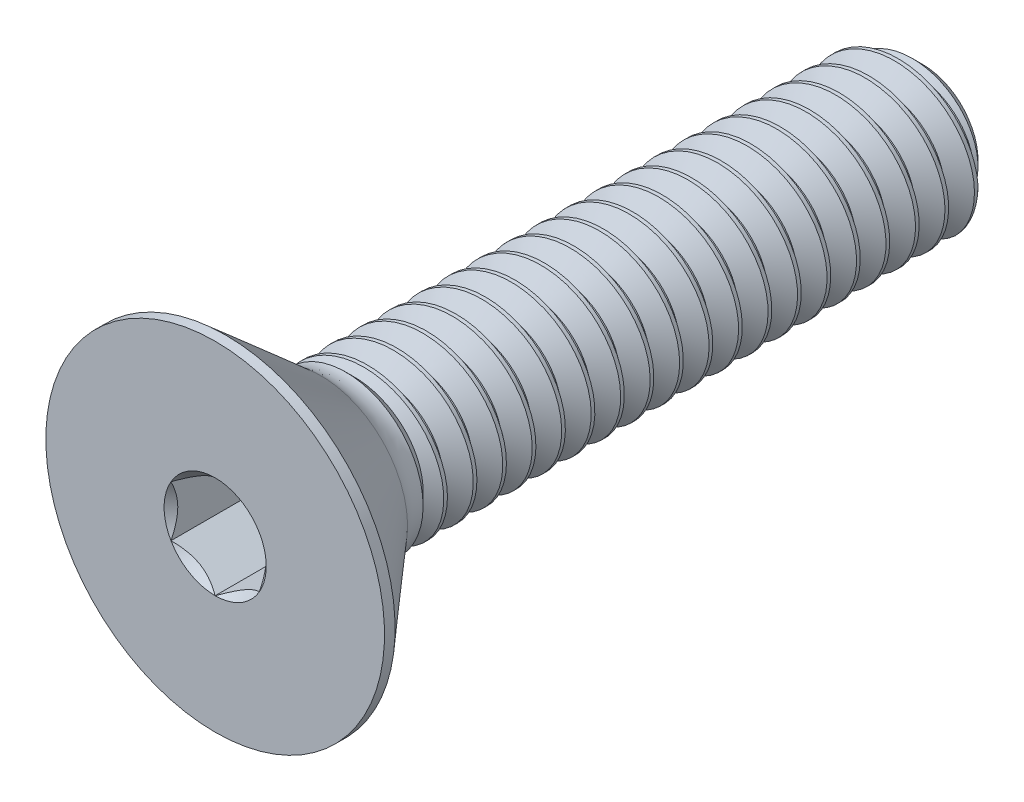
SolidWorks part; units mm, degrees
ref_plane "Front" through (0, 0, 0) normal (0, 0, 1) x (1, 0, 0)
ref_plane "Top" through (0, 0, 0) normal (0, 1, 0) x (1, 0, 0)
ref_plane "Right" through (0, 0, 0) normal (1, 0, 0) x (0, 0, -1)
sketch "Sketch1" plane through (0, 0, 0) normal (1, 0, 0) x (0, 0, -1)
  line L0 (0, 4.5593) -> (0.2845, 4.5593) construction
  line L1 (0.2845, 4.5593) -> (2.8448, 2.3336) construction
  line L2 (0, 2.0828) -> (19.05, 2.0828)
  line L3 (19.05, 2.0828) -> (19.05, 0)
  line L4 (19.05, 0) -> (0, 0)
  line L5 (0, 0) -> (0, 4.5593) construction
  line L6 (0, 4.5593) -> (0, -4.5593) construction
  line L7 (19.05, 2.0828) -> (19.05, -2.0828) construction
  line L8 (0, -4.5593) -> (0.2845, -4.5593) construction
  line L9 (0.2845, -4.5593) -> (2.8448, -2.3336) construction
  line L11 (0, 2.0828) -> (0, 0)
  line L12 (3.5157, 2.0828) -> (3.5157, 0) construction
  arc A1 (2.8448, 2.3336) -> (3.5157, 2.0828) centre (3.5157, 3.1055) ccw construction
  dimension "D1" = 0.2845
  dimension "Head Ht" = 2.8448
  dimension "Head Dia" = 9.1186
  dimension "Dia" = 4.1656
  dimension "Lg" = 19.05
  dimension "Head Angle" = 82
revolve "Revolve1" add sketch "Sketch1" angle 360 mid plane about L4
sketch "Sketch3" plane through (0, 0, -19.05) normal (0, 0, -1) x (-1, 0, 0)
  circle A0 centre (0, 0) radius 2.0828
curve "Helix/Spiral1" pitch 0.7937 height 19.05 radius 2.0828 centre (0, 0, -19.05) axis (0, 0, 1) start towards (0, 1, 0)
sketch "Sketch2" plane through (0, 0, 0) normal (1, 0, 0) x (0, 0, -1)
  line L0 (19.05, 2.0828) -> (19.7445, 2.0828)
  line L1 (19.7445, 2.0828) -> (19.4469, 1.5672)
  line L2 (19.4469, 1.5672) -> (19.3477, 1.5672)
  line L3 (19.3477, 1.5672) -> (19.05, 2.0828)
  line L4 (19.1988, 1.825) -> (19.5957, 1.825) construction
  dimension "D1" = 60
  dimension "D2" = 0.0992
  dimension "D3" = 0.3969
chamfer "Chamfer1" distance 0.5953 angle 45 1 edges at (0, 2.0828, -19.05)
sweep "Cut-Sweep1" cut profiles "Sketch2" path "Helix/Spiral1"
sketch "Sketch7" plane through (0, 0, 0) normal (1, 0, 0) x (0, 0, -1)
  line L0 (0, 4.5593) -> (0.2845, 4.5593) construction
  line L1 (0.2845, 4.5593) -> (2.8448, 2.3336) construction
  line L2 (0, 4.5593) -> (0.2845, 4.5593)
  line L3 (0.2845, 4.5593) -> (2.8448, 2.3336)
  line L4 (3.5157, 2.0828) -> (3.5157, 0) construction
  line L5 (3.5157, 2.0828) -> (3.5157, 0)
  line L7 (0, 0) -> (0, 4.5593) construction
  line L8 (0, 0) -> (0, 4.5593)
  line L9 (0, 0) -> (3.5157, 0)
  line L10 (5.0152, 0) -> (-5.0152, 0) construction
  arc A0 (2.8448, 2.3336) -> (3.5157, 2.0828) centre (3.5157, 3.1055) ccw construction
  arc A1 (2.8448, 2.3336) -> (3.5157, 2.0828) centre (3.5157, 3.1055) ccw
revolve "Revolve2" add sketch "Sketch7" angle 360 mid plane about L9
ref_plane "Plane1" through (0, 0, -3.5157) normal (0, 0, 1) x (1, 0, 0)
sketch "Sketch8" plane through (0, 0, -3.5157) normal (0, 0, 1) x (1, 0, 0)
  circle A0 centre (0, 0) radius 2.0828
extrude "Boss-Extrude1" add sketch "Sketch8" against normal through all draft 45
sketch "Sketch5" plane through (0, 0, 0) normal (0, 0, 1) x (1, 0, 0)
  line L1 (1.1906, -0.6874) -> (1.1906, 0.6874)
  line L2 (1.1906, 0.6874) -> (0, 1.3748)
  line L3 (0, 1.3748) -> (-1.1906, 0.6874)
  line L4 (-1.1906, 0.6874) -> (-1.1906, -0.6874)
  line L5 (-1.1906, -0.6874) -> (0, -1.3748)
  line L6 (0, -1.3748) -> (1.1906, -0.6874)
  circle A0 centre (0, 0) radius 1.1906 construction
  dimension "Hex" = 2.3813
extrude "Cut-Extrude2" cut sketch "Sketch5" against normal blind 1.9914
sketch "Sketch6" plane through (0, 0, 0) normal (0, 0, 1) x (1, 0, 0)
  circle A0 centre (0, 0) radius 1.3748
extrude "Cut-Extrude3" cut sketch "Sketch6" against normal blind 1.9914 draft 45
sketch "Sketch9" [suppressed] plane through (0, 0, -3.5157) normal (0, 0, 1) x (1, 0, 0)
  circle A1 centre (0, 0) radius 2.0828
  circle A2 centre (0, 0) radius 2.0828
  point P0 (0, 2.0828)
  dimension "D1" = 0
extrude "Boss-Extrude2" [suppressed] add sketch "Sketch9" against normal offset from surface (6.0093 mm away) 22.225 up to face at (0, 1.4875, -19.05)
sketch "Sketch10" plane through (0, 0, 0) normal (1, 0, 0) x (0, 0, -1)
  line L0 (19.05, 2.0828) -> (19.05, -2.0828) construction
  point P0 (17.8594, -2.0828)
  dimension "D1" = 1.1906
equation "\"D3@Helix/Spiral1\" = \"Lg@Sketch1\""
equation "\"D2@Sketch2\" = \"D4@Helix/Spiral1\" * .125"
equation "\"D3@Sketch2\" = \"D4@Helix/Spiral1\" * .5"
equation "\"D1@Chamfer1\" = \"D4@Helix/Spiral1\" * .75"
equation "\"D1@Cut-Extrude2\" = \"Head Ht@Sketch1\" * .7"
equation "\"D1@Sketch1\" = \"Head Ht@Sketch1\" * .1"
equation "\"D1@Sketch10\" = \"D4@Helix/Spiral1\" * 1.5"
equation "\"D1@Cut-Extrude3\" = \"D1@Cut-Extrude2\""
